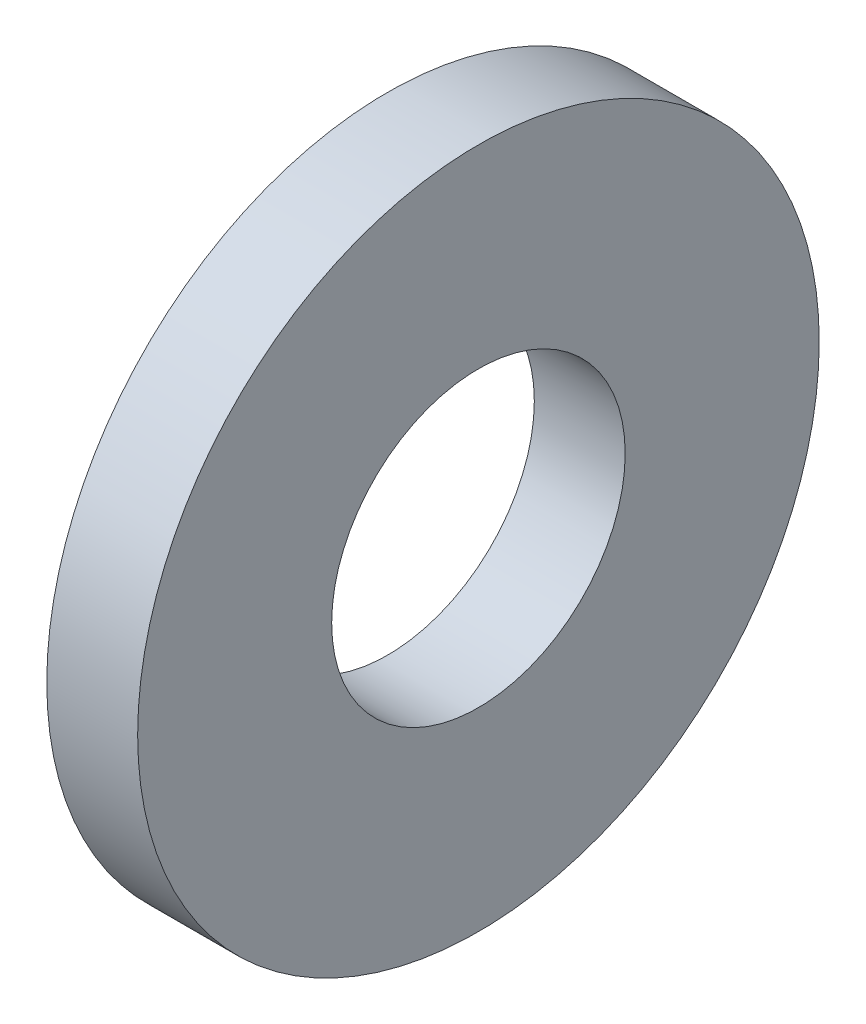
SolidWorks part; units mm, degrees
ref_plane "Front Plane" through (0, 0, 0) normal (0, 0, 1) x (1, 0, 0)
ref_plane "Top Plane" through (0, 0, 0) normal (0, 1, 0) x (1, 0, 0)
ref_plane "Right Plane" through (0, 0, 0) normal (1, 0, 0) x (0, 0, -1)
sketch "Sketch1" plane through (0, 0, 0) normal (1, 0, 0) x (0, 0, -1)
  circle A0 centre (0, 0) radius 4.1021
  circle A1 centre (0, 0) radius 9.525
  dimension "D1" = 19.05
  dimension "D2" = 8.2042
extrude "Boss-Extrude1" add sketch "Sketch1" along normal blind 2.54
